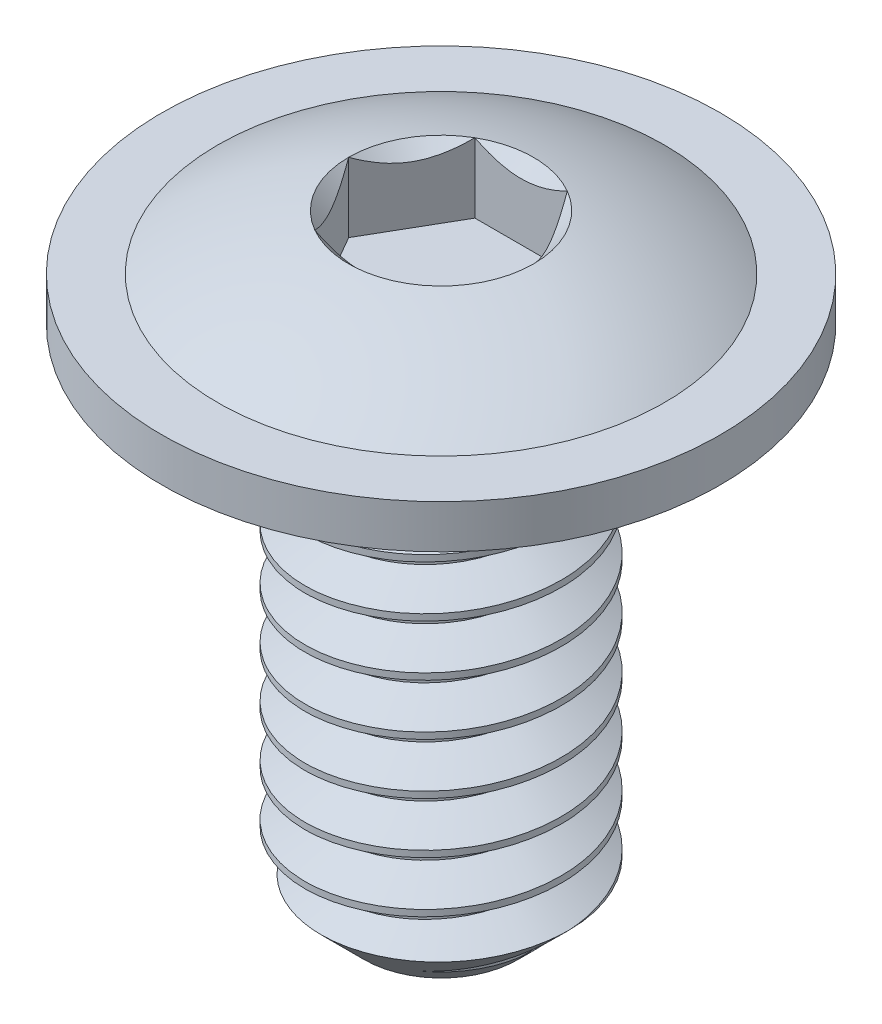
SolidWorks part; units mm, degrees
ref_plane "Front Plane" through (0, 0, 0) normal (0, 0, 1) x (1, 0, 0)
ref_plane "Top Plane" through (0, 0, 0) normal (0, 1, 0) x (1, 0, 0)
ref_plane "Right Plane" through (0, 0, 0) normal (1, 0, 0) x (0, 0, -1)
sketch "Sketch1" plane through (0, 0, 0) normal (0, 0, 1) x (1, 0, 0)
  line L0 (0, 0) -> (0, 53.1234) construction
  line L1 (0, 0) -> (-3.175, 0)
  line L2 (-3.175, 0) -> (-3.175, 12.7)
  line L3 (-3.175, 12.7) -> (-6.9215, 12.7)
  line L4 (-6.9215, 12.7) -> (-6.9215, 13.777)
  line L5 (-6.9215, 13.777) -> (-5.5372, 13.777)
  line L6 (0, 0) -> (0, 15.3924)
  arc A0 (-5.5372, 13.777) -> (0, 15.3924) centre (0, 5.0948) cw
  dimension "screw od" = 6.35
  dimension "head od" = 13.843
  dimension "D3" = 11.0744
  dimension "D4" = 1.077
  dimension "head height" = 2.6924
  dimension "screw length" = 12.7
sketch "Sketch2" plane through (0, 0, 0) normal (0, 0, 1) x (1, 0, 0)
  line L0 (0, 0) -> (0, 15.3924) construction
  line L1 (-3.175, 12.7) -> (-6.9215, 12.7) construction
  line L2 (0, 0) -> (-3.175, 0) construction
  line L3 (-3.175, 0) -> (-3.175, 12.7) construction
  line L4 (0, 0) -> (0, 12.7)
  line L5 (0, 12.7) -> (-3.175, 12.7)
  line L6 (0, 0) -> (-3.175, 0)
  line L7 (-3.175, 0) -> (-3.175, 12.7)
revolve "Revolve2" add sketch "Sketch2" angle 360 about L0
sketch "Sketch3" plane through (0, 12.7, 0) normal (0, 1, 0) x (1, 0, 0)
  circle A1 centre (0, 0) radius 3.175
  circle A2 centre (0, 0) radius 3.175
  dimension "D1" = 0
curve "Helix/Spiral1" pitch 1.27 height 17.4625 turns 13.75 parameters "pitch"=1.27
chamfer "Chamfer1" distance 1.27 angle 45 1 edges at (0, 0, -3.175)
sketch "Sketch4" plane through (0, 0, 0) normal (0, 0, 1) x (1, 0, 0)
  line L0 (3.175, 13.8112) -> (3.175, 12.7)
  line L1 (3.175, 12.7) -> (2.3501, 13.1762)
  line L2 (2.3501, 13.1762) -> (2.3501, 13.335)
  line L3 (2.3501, 13.335) -> (3.175, 13.8112)
  line L4 (2.3501, 13.2556) -> (3.175, 13.2556) construction
  line L5 (2.7626, 12.9381) -> (2.7626, 13.5731) construction
  line L7 (3.175, 12.7) -> (-3.175, 12.7) construction
  dimension "D1" = 60
  dimension "D2" = 0.1588
  dimension "D3" = 0.635
sweep "Cut-Sweep1" cut profiles "Sketch4" path "Helix/Spiral1"
sketch "Sketch5" plane through (0, 0, 0) normal (0, 0, 1) x (1, 0, 0)
  line L0 (0, 0) -> (0, 15.3924) construction
  line L1 (-3.175, 12.7) -> (-6.9215, 12.7) construction
  line L2 (-6.9215, 13.777) -> (-5.5372, 13.777) construction
  line L3 (-6.9215, 12.7) -> (-6.9215, 13.777) construction
  line L4 (0, 12.7) -> (0, 15.3924)
  line L5 (0, 12.7) -> (-6.9215, 12.7)
  line L6 (-6.9215, 13.777) -> (-5.5372, 13.777)
  line L7 (-6.9215, 12.7) -> (-6.9215, 13.777)
  arc A0 (0, 15.3924) -> (-5.5372, 13.777) centre (0, 5.0948) ccw construction
  arc A1 (0, 15.3924) -> (-5.5372, 13.777) centre (0, 5.0948) ccw
revolve "Revolve3" add sketch "Sketch5" angle 360 about L0
ref_plane "Plane1" through (0, 15.3924, 0) normal (0, 1, 0) x (-1, 0, 0)
sketch "Sketch6" plane through (0, 15.3924, 0) normal (0, 1, 0) x (-1, 0, 0)
  line L1 (1.1457, 1.9844) -> (-1.1457, 1.9844)
  line L2 (-1.1457, 1.9844) -> (-2.2914, 0)
  line L3 (-2.2914, 0) -> (-1.1457, -1.9844)
  line L4 (-1.1457, -1.9844) -> (1.1457, -1.9844)
  line L5 (1.1457, -1.9844) -> (2.2914, 0)
  line L6 (2.2914, 0) -> (1.1457, 1.9844)
  circle A0 centre (0, 0) radius 1.9844 construction
  dimension "hex" = 3.9688
extrude "Cut-Extrude1" cut sketch "Sketch6" against normal blind 1.9844
ref_plane "Plane2" through (0, 15.1342, 0) normal (0, 1, 0) x (-1, 0, 0)
sketch "Sketch7" plane through (0, 15.1342, 0) normal (0, 1, 0) x (-1, 0, 0)
  circle A0 centre (0, 0) radius 2.2914
extrude "Cut-Extrude2" cut sketch "Sketch7" against normal up to surface (1.7262 mm away) draft 45 and the other way through all
ref_plane "Plane3" through (0, 3.175, 0) normal (0, -1, 0) x (1, 0, 0)
equation "\"D2@Sketch4\" = \"pitch@Helix/Spiral1\"*.125"
equation "\"D3@Sketch4\" = \"pitch@Helix/Spiral1\"*.5"
equation "\"D3@Helix/Spiral1\" = \"screw length@Sketch1\"+.18750"
equation "\"D1@Chamfer1\" = \"pitch@Helix/Spiral1\""
equation "\"D1@Cut-Extrude1\" = \"hex@Sketch6\"/2"
equation "\"D1@Sketch8\" = \"screw od@Sketch1\""
equation "\"D4@Sketch1\" = \"head height@Sketch1\"/2.5"
equation "\"D3@Sketch1\" = \"head od@Sketch1\"*.8"
equation "\"D5@Sketch10\" = \"screw od@Sketch1\""
equation "\"D4@Sketch10\" = \"D1@Sketch10\"*.2"
equation "\"D5@Sketch13\" = \"D1@Sketch13\"*.2"
equation "\"D5@Sketch16\" = \"D3@Sketch16\"*.2"
equation "\"D4@Sketch18\" = \"D3@Sketch18\"*.2"
